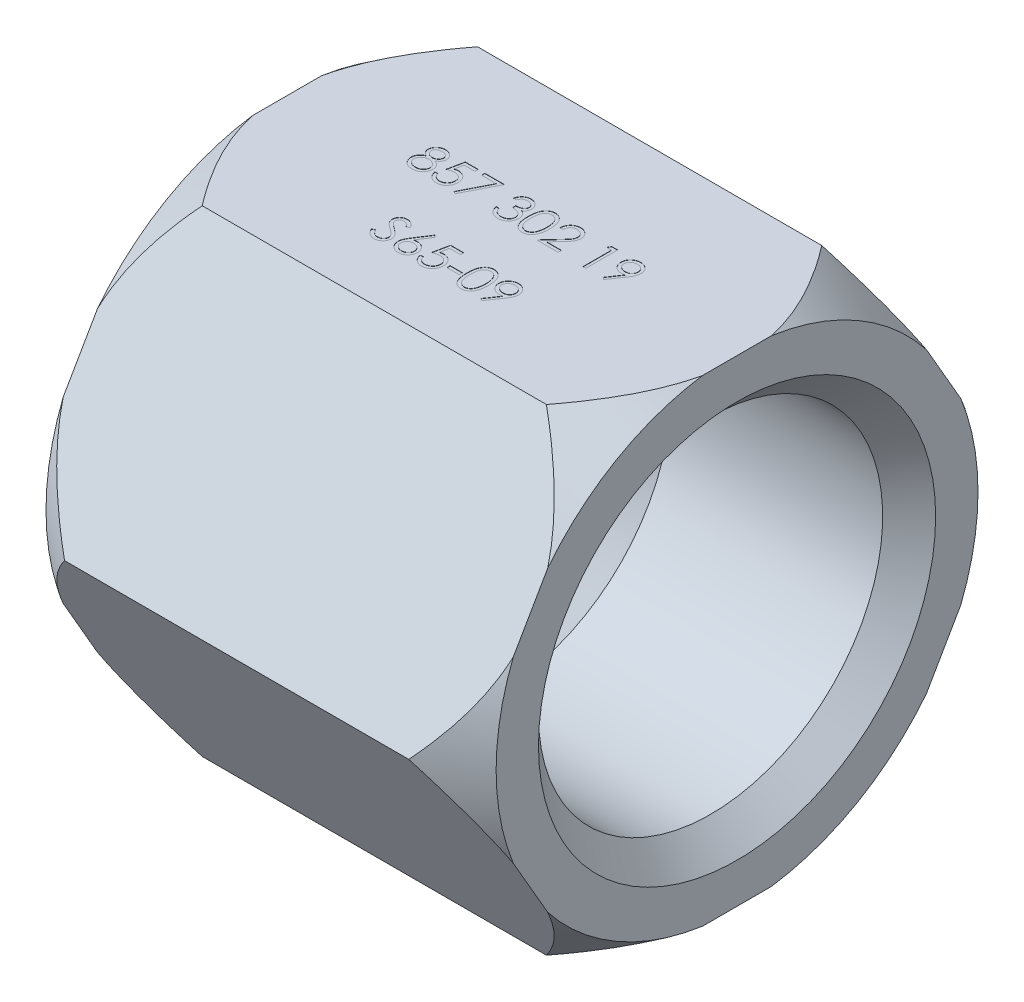
SolidWorks part; units mm, degrees
material "Plain Carbon Steel"
ref_plane "Front Plane" through (0, 0, 0) normal (0, 0, 1) x (1, 0, 0)
ref_plane "Top Plane" through (0, 0, 0) normal (0, 1, 0) x (1, 0, 0)
ref_plane "Right Plane" through (0, 0, 0) normal (1, 0, 0) x (0, 0, -1)
sketch "Sketch1" plane through (0, 0, 0) normal (0, 0, 1) x (1, 0, 0)
  line L0 (0, 0) -> (32.0688, 0) construction
  line L1 (0, 0) -> (0, 9.1)
  line L2 (0, 9.1) -> (2, 10.4)
  line L3 (2, 10.4) -> (15, 10.4)
  line L4 (15, 10.4) -> (17, 9.1)
  line L5 (17, 9.1) -> (17, 6.5)
  line L6 (17, 6.5) -> (8, 6.5)
  line L7 (8, 6.5) -> (3, 2.7322)
  line L9 (0, 0) -> (1.3583, 0)
  line L11 (3, 2.7322) -> (1.3583, 0)
  dimension "D2" = 14
  dimension "D3" = 17
  dimension "D4" = 18.2
  dimension "D5" = 20.8
  dimension "D7" = 2
  dimension "D6" = 2
  dimension "D8" = 13
  dimension "D9" = 9
  dimension "D10" = 59
  dimension "D11" = 37
revolve "Revolve1" add sketch "Sketch1" angle 360 about L0
sketch "Sketch2" plane through (17, 0, 0) normal (1, 0, 0) x (0, 0, -1)
  line L1 (5.2, 9.0067) -> (-5.2, 9.0067)
  line L2 (-5.2, 9.0067) -> (-10.4, 0)
  line L3 (-10.4, 0) -> (-5.2, -9.0067)
  line L4 (-5.2, -9.0067) -> (5.2, -9.0067)
  line L5 (5.2, -9.0067) -> (10.4, 0)
  line L6 (10.4, 0) -> (5.2, 9.0067)
  circle A0 centre (0, 0) radius 9.0067 construction
  circle A1 centre (0, 0) radius 10.4 construction
extrude "Extrude1" cut sketch "Sketch2" against normal up to surface (17 mm away) flip side to cut up to face at (0, 0, 9.1)
chamfer "Chamfer1" distance 1 angle 45 1 edges at (17, 0, 6.5)
sketch "Sketch3" plane through (0, 9.0067, 0) normal (0, 1, 0) x (1, 0, 0)
  line L0 (1.4004, 0) -> (15.5171, 0) construction
  text T0 "857 302 19\r\nS65-09" font "Century Gothic" height 1.2
extrude "Cut-Extrude1" cut sketch "Sketch3" against normal blind 0.01
